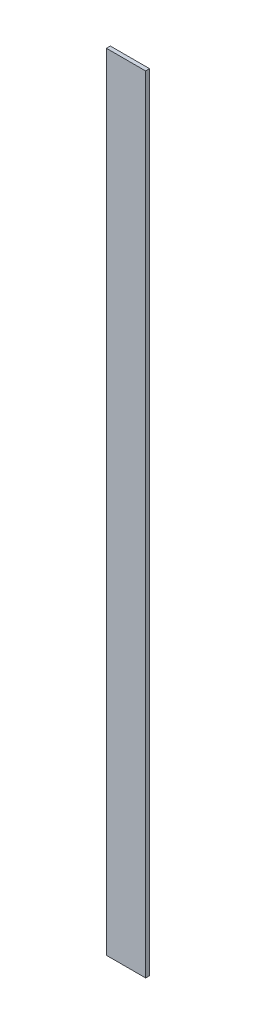
SolidWorks part; units mm, degrees
ref_plane "Спереди" through (0, 0, 0) normal (0, 0, 1) x (1, 0, 0)
ref_plane "Сверху" through (0, 0, 0) normal (0, 1, 0) x (1, 0, 0)
ref_plane "Справа" through (0, 0, 0) normal (1, 0, 0) x (0, 0, -1)
sketch "Эскиз1" plane through (0, 0, 0) normal (0, 1, 0) x (1, 0, 0)
  line L0 (0, 45) -> (0, 0)
  line L1 (0, 0) -> (45, 0)
extrude "Вытянуть-Тонкостенный1" add sketch "Эскиз1" along normal blind 1000 thin thin type one direction wall 5
sketch "Эскиз2" plane through (-5, 0, 0) normal (-1, 0, 0) x (0, 0, 1)
  line L0 (0, 0) -> (-45, 45)
  line L1 (-45, 1000) -> (-45, 0) construction
  line L2 (-45, 0) -> (-45, 45)
  line L3 (-45, 0) -> (0, 0)
  line L4 (-45, 500) -> (36.3553, 500) construction
  line L5 (-45, 1000) -> (0, 1000)
  line L6 (-45, 1000) -> (-45, 955)
  line L7 (0, 1000) -> (-45, 955)
extrude "Вырез-Вытянуть1" cut sketch "Эскиз2" against normal through all
